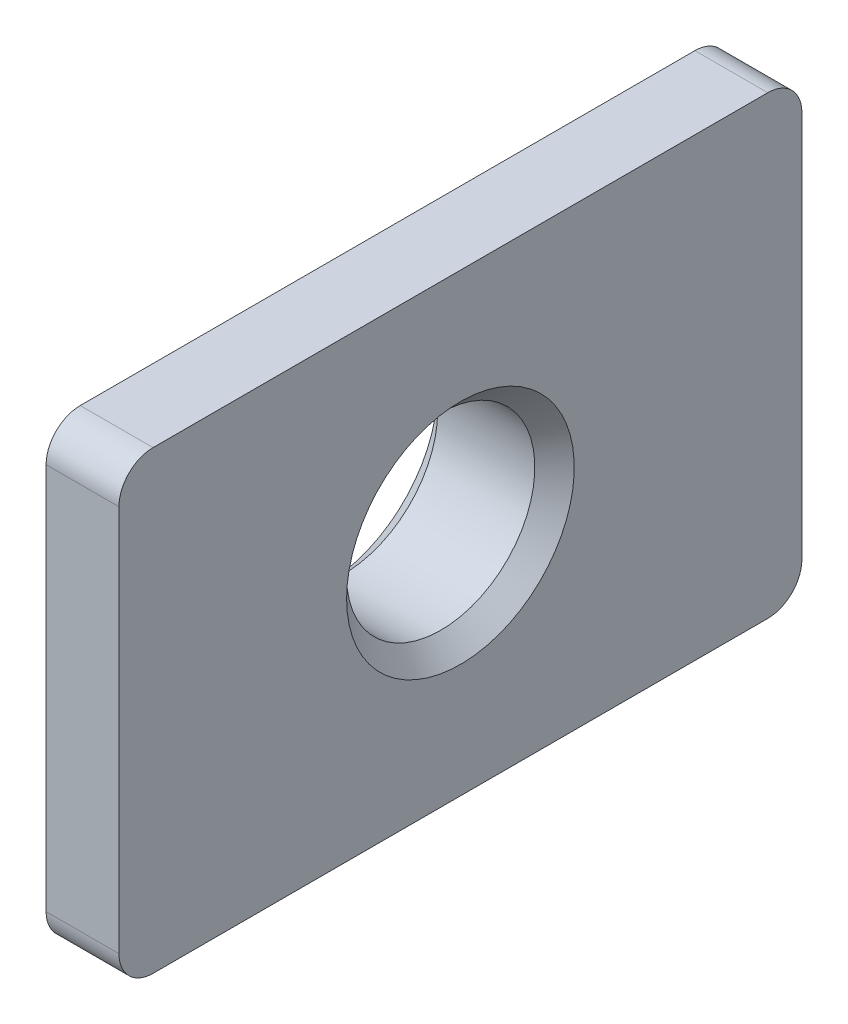
SolidWorks part; units mm, degrees
ref_plane "Front Plane" through (0, 0, 0) normal (0, 0, 1) x (1, 0, 0)
ref_plane "Top Plane" through (0, 0, 0) normal (0, 1, 0) x (1, 0, 0)
ref_plane "Right Plane" through (0, 0, 0) normal (1, 0, 0) x (0, 0, -1)
ref_plane "Plane1" through (-1.6, 0, 0) normal (-1, 0, 0) x (0, -1, 0)
sketch "Sketch1" plane through (-1.6, 0, 0) normal (-1, 0, 0) x (0, -1, 0)
  line L0 (4.25, 7.5) -> (-4.25, 7.5)
  line L1 (-5, 6.75) -> (-5, -6.75)
  line L2 (-4.25, -7.5) -> (4.25, -7.5)
  line L3 (5, -6.75) -> (5, 6.75)
  arc A0 (-4.25, 7.5) -> (-5, 6.75) centre (-4.25, 6.75) ccw
  arc A1 (-5, -6.75) -> (-4.25, -7.5) centre (-4.25, -6.75) ccw
  arc A2 (4.25, -7.5) -> (5, -6.75) centre (4.25, -6.75) ccw
  arc A3 (5, 6.75) -> (4.25, 7.5) centre (4.25, 6.75) ccw
extrude "Boss-Extrude1" add sketch "Sketch1" against normal blind 1.6
ref_plane "Plane2" through (-3, 0, 0) normal (-1, 0, 0) x (0, -1, 0)
sketch "Sketch2" plane through (-3, 0, 0) normal (-1, 0, 0) x (0, -1, 0)
  circle A0 centre (0, 0) radius 3.45
extrude "Boss-Extrude2" add sketch "Sketch2" against normal up to surface (1.4 mm away) up to face at (-1.6, 0, 0)
hole_wizard "M3.5 Clearance Hole1" positions "Sketch4" profile "Sketch3" hole size "M3.5" standard "ANSI Metric"
sketch "Sketch4" plane through (-3, 0, 0) normal (-1, 0, 0) x (0, 0, 1)
  point P0 (0, 0)
sketch "Sketch3" plane through (-3, 0, 0) normal (0, 1, 0) x (0, 0, 1)
  line L0 (0, 0) -> (0, 3)
  line L1 (0, 3) -> (2.067, 3)
  line L2 (2.067, 3) -> (2.067, 0)
  line L5 (2.067, 0) -> (0, 0)
  line L11 (0, -6.35) -> (0, 107.95) construction
  dimension "Thru Hole Dia." = 4.134
  dimension "Thru Hole Depth" = 3
chamfer "Chamfer1" distance 0.433 angle 45 1 edges at (-3, 0, 2.067)
chamfer "Chamfer2" distance 0.433 angle 45 1 edges at (0, 0, 2.067)
ref_axis "Axis1" through (1.3774, 0, 0) along (-1, 0, 0)
ref_plane "Plane3" through (0, 0, 0) normal (0, -1, 0) x (-1, 0, 0)
